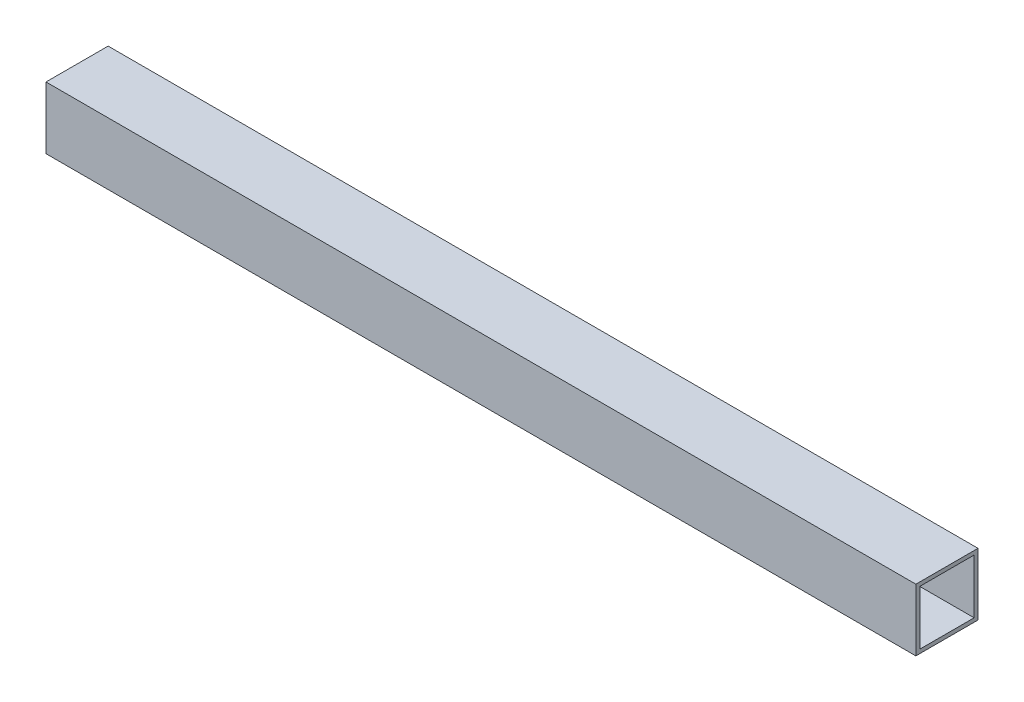
SolidWorks part; units mm, degrees
material "6061-T6 (SS)"
ref_plane "Front" through (0, 0, 0) normal (0, 0, 1) x (1, 0, 0)
ref_plane "Top" through (0, 0, 0) normal (0, 1, 0) x (1, 0, 0)
ref_plane "Right" through (0, 0, 0) normal (1, 0, 0) x (0, 0, -1)
sketch "Sketch1" plane through (0, 0, 0) normal (1, 0, 0) x (0, 0, -1)
  line L1 (-12.7, -12.7) -> (12.7, -12.7)
  line L2 (-12.7, -12.7) -> (-12.7, 12.7)
  line L3 (-12.7, 12.7) -> (12.7, 12.7)
  line L4 (12.7, -12.7) -> (12.7, 12.7)
  line L5 (-12.7, -12.7) -> (12.7, 12.7) construction
  line L6 (-12.7, 12.7) -> (12.7, -12.7) construction
  point P0 (0, 0)
  dimension "D1" = 25.4
extrude "Extrude-Thin1" add sketch "Sketch1" along normal up to surface (355.6 mm away) thin thin type one direction reverse wall 1.5875
